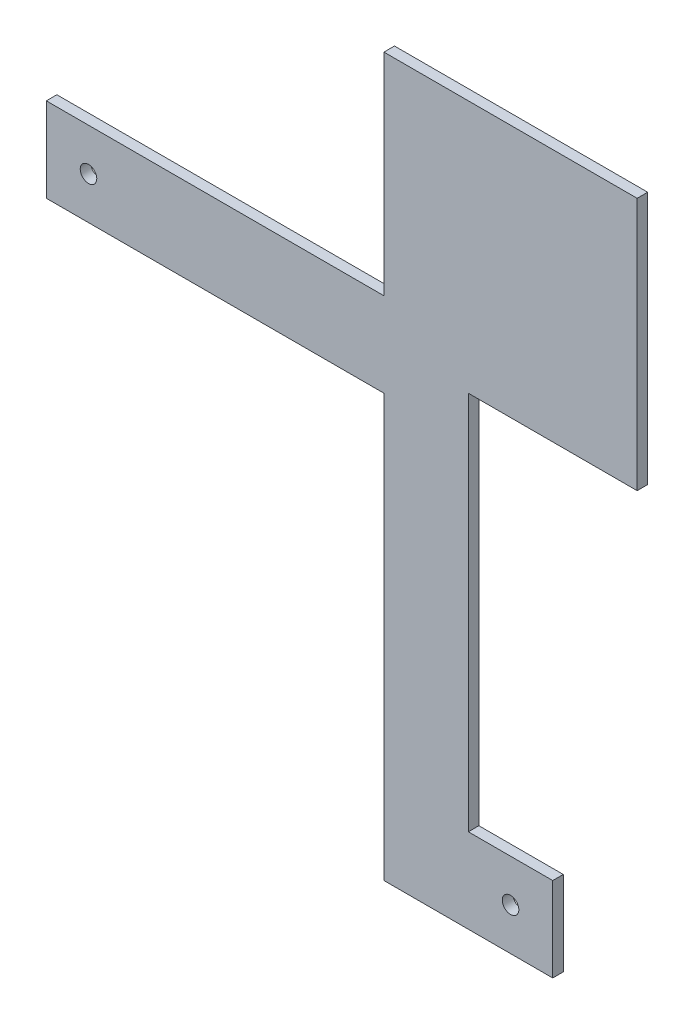
SolidWorks part; units mm, degrees
ref_plane "Front Plane" through (0, 0, 0) normal (1, 0, 0) x (0, 1, 0)
ref_plane "Top Plane" through (0, 0, 0) normal (0, 0, 1) x (0, 1, 0)
ref_plane "Right Plane" through (0, 0, 0) normal (0, 1, 0) x (-1, 0, 0)
sketch "Sketch1" plane through (0, 0, 0) normal (0, 0, 1) x (0, 1, 0)
  line L1 (-107.95, -12.7) -> (107.95, -12.7) construction
  line L2 (-107.95, -12.7) -> (-107.95, 12.7) construction
  line L3 (-107.95, 12.7) -> (107.95, 12.7) construction
  line L4 (107.95, -12.7) -> (107.95, 12.7) construction
  line L5 (-107.95, -12.7) -> (107.95, 12.7) construction
  line L6 (-107.95, 12.7) -> (107.95, -12.7) construction
  line L7 (-107.95, -12.7) -> (-82.55, -12.7) construction
  line L8 (-107.95, -12.7) -> (-107.95, -38.1) construction
  line L9 (-107.95, -38.1) -> (-82.55, -38.1) construction
  line L10 (-82.55, -12.7) -> (-82.55, -38.1) construction
  line L13 (-82.55, -12.7) -> (-82.55, -38.1)
  line L14 (-82.55, -38.1) -> (-107.95, -38.1)
  line L15 (-107.95, -38.1) -> (-107.95, 12.7)
  line L17 (19.05, 12.7) -> (44.45, 12.7) construction
  line L18 (19.05, 12.7) -> (19.05, 114.3) construction
  line L19 (19.05, 114.3) -> (44.45, 114.3) construction
  line L20 (44.45, 12.7) -> (44.45, 114.3) construction
  line L21 (44.45, 12.7) -> (44.45, 114.3)
  line L22 (44.45, 114.3) -> (19.05, 114.3)
  line L23 (19.05, 114.3) -> (19.05, 12.7)
  line L24 (19.05, 12.7) -> (-107.95, 12.7)
  line L25 (-82.55, -12.7) -> (31.75, -12.7)
  line L26 (31.75, -12.7) -> (107.95, -12.7) construction
  line L27 (31.75, -12.7) -> (31.75, -63.5) construction
  line L29 (107.95, -12.7) -> (107.95, -63.5) construction
  line L34 (31.75, -12.7) -> (31.75, -63.5)
  line L35 (31.75, -63.5) -> (107.95, -63.5)
  line L39 (107.95, -63.5) -> (107.95, 12.7)
  line L40 (107.95, 12.7) -> (44.45, 12.7)
  point P0 (0, 0)
  point P17 (31.75, -38.1)
  dimension "D1" = 215.9
  dimension "D2" = 25.4
  dimension "D3" = 25.4
  dimension "D4" = 25.4
  dimension "D5" = 101.6
  dimension "D6" = 25.4
  dimension "D7" = 127
  dimension "D8" = 139.7
  dimension "D9" = 50.8
extrude "Boss-Extrude1" add sketch "Sketch1" along normal blind 3.175
sketch "Sketch2" plane through (0, 0, 3.175) normal (0, 0, 1) x (1, 0, 0)
  line L0 (38.1, -107.95) -> (38.1, -82.55) construction
  line L1 (-12.7, -107.95) -> (38.1, -107.95) construction
  line L2 (-114.3, 44.45) -> (-114.3, 19.05) construction
  line L3 (-114.3, 19.05) -> (-12.7, 19.05) construction
  point P0 (25.4, -95.25)
  point P1 (-153.252, -35.1554)
  point P6 (-101.6, 31.75)
  point P8 (-174.4616, 15.3753)
  dimension "D1" = 12.7
  dimension "D2" = 12.7
  dimension "D3" = 12.7
  dimension "D4" = 12.7
hole_wizard "#9 (0.196) Diameter Hole1" positions "Sketch2" profile "Sketch3" hole size "#9" standard "ANSI Inch" end condition through all
sketch "Sketch3" plane through (25.4, -95.25, 3.175) normal (1, 0, 0) x (0, -1, 0)
  line L0 (0, 0) -> (0, 3.175)
  line L1 (0, 3.175) -> (2.4892, 3.175)
  line L2 (2.4892, 3.175) -> (2.4892, 0)
  line L5 (2.4892, 0) -> (0, 0)
  line L11 (0, -6.35) -> (0, 107.95) construction
  dimension "Thru Hole Dia." = 4.9784
  dimension "Thru Hole Depth" = 3.175
